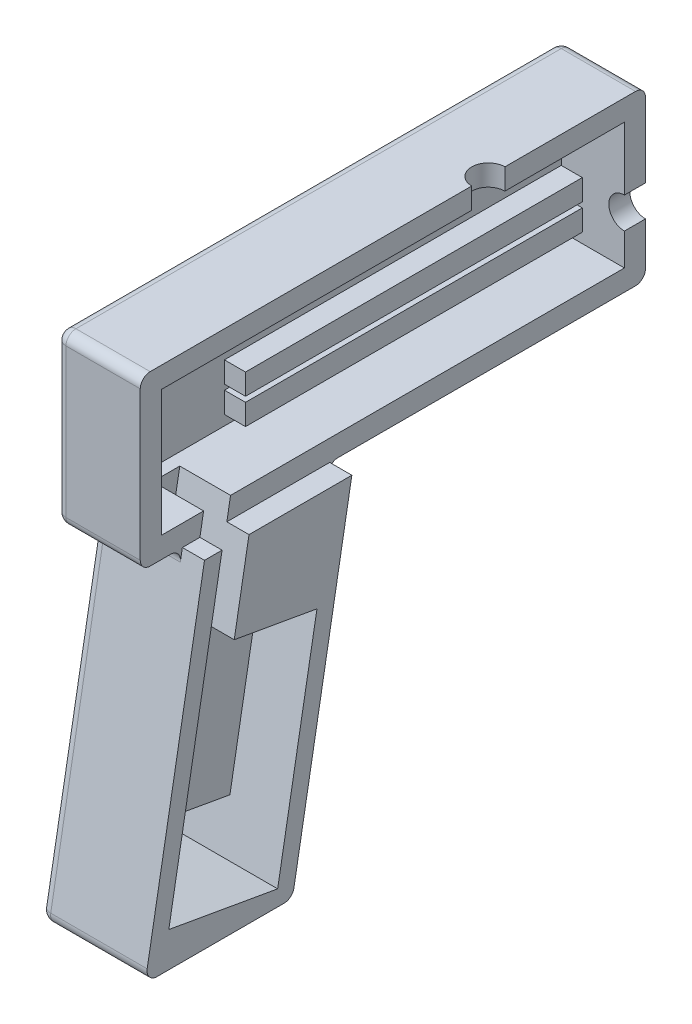
SolidWorks part; units mm, degrees
ref_plane "Front Plane" through (0, 0, 0) normal (0, 0, 1) x (1, 0, 0)
ref_plane "Top Plane" through (0, 0, 0) normal (0, 1, 0) x (1, 0, 0)
ref_plane "Right Plane" through (0, 0, 0) normal (1, 0, 0) x (0, 0, -1)
sketch "Sketch1" plane through (0, 0, 0) normal (0, 0, 1) x (1, 0, 0)
  line L1 (0, 0) -> (25.4, 0)
  line L2 (0, 0) -> (0, 50.8)
  line L3 (0, 50.8) -> (25.4, 50.8)
  line L4 (25.4, 0) -> (25.4, 50.8)
  dimension "D1" = 50.8
  dimension "D2" = 25.4
extrude "Boss-Extrude1" add sketch "Sketch1" against normal blind 152.4
sketch "Sketch2" plane through (25.4, 0, 0) normal (1, 0, 0) x (0, 0, -1)
  line L0 (0, 0) -> (0, 50.8) construction
  line L1 (6.35, 44.45) -> (146.05, 44.45)
  line L2 (6.35, 44.45) -> (6.35, 6.35)
  line L3 (6.35, 6.35) -> (146.05, 6.35)
  line L4 (146.05, 44.45) -> (146.05, 6.35)
  line L5 (152.4, 50.8) -> (0, 50.8) construction
  line L6 (152.4, 0) -> (0, 0) construction
  line L7 (152.4, 0) -> (152.4, 50.8) construction
  point P12 (6.35, 25.4)
  point P13 (0, 25.4)
  dimension "D1" = 6.35
  dimension "D2" = 6.35
  dimension "D3" = 6.35
  dimension "D4" = 6.35
extrude "Cut-Extrude1" cut sketch "Sketch2" against normal blind 19.05
sketch "Sketch4" plane through (0, 50.8, 0) normal (0, 1, 0) x (1, 0, 0)
  line L1 (25.4, 152.4) -> (25.4, 0) construction
  line L6 (0, 0) -> (25.4, 0)
  line L7 (25.4, 0) -> (25.4, 152.4)
  line L8 (25.4, 152.4) -> (0, 152.4)
  line L9 (0, 152.4) -> (0, 0)
  line L11 (25.4, 100) -> (25.4, 110)
  arc A1 (25.4, 100) -> (25.4, 110) centre (25.4, 105) cw
  dimension "D1" = 100
  dimension "D2" = 0
extrude "HitLED" cut sketch "Sketch4" against normal up to vertex (6.35 mm away) contours L11 A1 up to point (25.4, 44.45, -146.05)
sketch "Sketch5" plane through (6.35, 0, 0) normal (1, 0, 0) x (0, 0, -1)
  line L0 (44.45, 17.27) -> (146.05, 17.27)
  line L1 (44.45, 23.62) -> (146.05, 23.62)
  line L2 (44.45, 23.62) -> (44.45, 9.35)
  line L3 (44.45, 9.35) -> (146.05, 9.35)
  line L4 (146.05, 23.62) -> (146.05, 9.35)
  line L9 (44.45, 15.7) -> (146.05, 15.7)
  line L10 (6.35, 6.35) -> (146.05, 6.35) construction
  line L11 (146.05, 6.35) -> (146.05, 44.45) construction
  point P8 (0, 0)
  point P9 (0, 0)
  line M13 (146.05, 6.35) -> (146.05, 44.45)
  dimension "D1" = 1.57
  dimension "D2" = 6.35
  dimension "D3" = 6.35
  dimension "D4" = 3
  dimension "D5" = 0
  dimension "D6" = 101.6
extrude "PCB Slot" add sketch "Sketch5" along normal blind 6.35 contours L1 L2 L0 M13 | L9 L2 L3 M13 region at (6.35, 20.445, -95.25) region at (6.35, 12.525, -95.25)
sketch "Sketch7" plane through (0, 0, -146.05) normal (0, 0, 1) x (1, 0, 0)
  line L0 (25.4, 6.35) -> (25.4, 44.45) construction
  line L1 (25.4, 25.4) -> (25.4, 16)
  arc A0 (25.4, 16) -> (25.4, 25.4) centre (25.4, 20.7) cw
extrude "IRLED" cut sketch "Sketch7" against normal blind 6.35
sketch "Sketch8" plane through (0, 0, 0) normal (0, -1, 0) x (-1, 0, 0)
  line L0 (-25.4, 152.4) -> (-25.4, 0) construction
  line L1 (-25.4, 12.7) -> (-12.7, 12.7)
  line L2 (-25.4, 12.7) -> (-25.4, 57.15)
  line L3 (-25.4, 57.15) -> (-12.7, 57.15)
  line L4 (-12.7, 12.7) -> (-12.7, 57.15)
  line L5 (0, 152.4) -> (0, 0) construction
  line L6 (0, 0) -> (-25.4, 0) construction
  dimension "D1" = 12.7
  dimension "D2" = 44.45
  dimension "D3" = 12.7
extrude "HandleHole" cut sketch "Sketch8" against normal blind 6.35
sketch "Sketch10" plane through (25.4, 0, 0) normal (1, 0, 0) x (0, 0, -1)
  line L0 (12.7, 0) -> (-5.2148, -101.6)
  line L1 (-5.2148, -101.6) -> (39.2352, -101.6)
  line L2 (39.2352, -101.6) -> (57.15, 0)
  line L4 (12.7, 0) -> (57.15, 0)
  dimension "D1" = 101.6
extrude "Butt" add sketch "Sketch10" against normal up to surface (25.4 mm away) separate body up to face at (0, 25.4, -76.2)
sketch "Sketch11" plane through (25.4, 0, 0) normal (1, 0, 0) x (0, 0, -1)
  line L0 (24.1444, -25.6759) -> (23.8454, -25.6232)
  line L3 (13.7936, -23.8507) -> (1.9399, -91.0762)
  line L4 (13.7936, -23.8507) -> (46.6246, -29.6397)
  line L5 (1.9399, -91.0762) -> (34.7709, -96.8652)
  line L6 (46.6246, -29.6397) -> (34.7709, -96.8652)
  line L7 (39.2352, -101.6) -> (57.15, 0) construction
  line L8 (12.7, 0) -> (-5.2148, -101.6) construction
  dimension "D1" = 68.2625
  dimension "D2" = 33.3375
  dimension "D3" = 5.2186
extrude "BatteryPack" cut sketch "Sketch11" against normal blind 10.3187 contours L6 L4 L0 L3 L5 region at (25.4, -60.358, -24.2823)
sketch "Sketch13" plane through (15.0812, 0, 0) normal (1, 0, 0) x (0, 0, -1)
  line L0 (13.7936, -23.8507) -> (1.9399, -91.0762)
  line L1 (13.7936, -23.8507) -> (21.672, -25.2399)
  line L2 (1.9399, -91.0762) -> (9.8184, -92.4654)
  line L3 (21.672, -25.2399) -> (9.8184, -92.4654)
  line L4 (1.9399, -91.0762) -> (34.7709, -96.8652) construction
  line L5 (13.7936, -23.8507) -> (1.9399, -91.0762) construction
  line L6 (13.7936, -23.8507) -> (46.6246, -29.6397) construction
  line L7 (13.7936, -23.8507) -> (21.672, -25.2399)
  line L8 (13.7936, -23.8507) -> (21.672, -25.2399)
  line L9 (9.8184, -92.4654) -> (1.9399, -91.0762)
  line M6 (46.6246, -29.6397) -> (13.7936, -23.8507)
  line M7 (13.7936, -23.8507) -> (1.9399, -91.0762)
  line M8 (1.9399, -91.0762) -> (34.7709, -96.8652)
  dimension "D1" = 0
  dimension "D2" = 0
  dimension "D3" = 8
  dimension "D4" = 0
extrude "Wires-Battery" cut sketch "Sketch13" against normal blind 5 contours L3 M6 M7 M8 region at (15.0812, -58.1581, -11.806)
sketch "Sketch21" plane through (25.4, 0, 0) normal (1, 0, 0) x (0, 0, -1)
  line L0 (13.7936, -23.8507) -> (21.672, -25.2399)
  line L1 (13.7936, -23.8507) -> (46.6246, -29.6397) construction
  line L2 (21.672, -25.2399) -> (26.1225, 0)
  line L3 (57.15, 0) -> (12.7, 0) construction
  line L4 (26.1225, 0) -> (17.9991, 0)
  line L5 (17.9991, 0) -> (13.7936, -23.8507)
  line L6 (21.672, -25.2399) -> (9.8184, -92.4654) construction
  line L7 (13.7936, -23.8507) -> (1.9399, -91.0762) construction
  dimension "D1" = 8
extrude "Wire-Track" cut sketch "Sketch21" against normal up to surface (15.3187 mm away) contours L5 L0 L2 L4 up to face at (10.0813, -58.1581, -11.806)
sketch "Sketch23" plane through (0, 0, -12.7) normal (0, 0, -1) x (-1, 0, 0)
  line L1 (-12.7, 6.35) -> (-25.4, 6.35)
  line L2 (-12.7, 6.35) -> (-12.7, 0)
  line L3 (-12.7, 0) -> (-25.4, 0)
  line L4 (-25.4, 6.35) -> (-25.4, 0)
extrude "FixHandleHole" add sketch "Sketch23" along normal up to next
sketch "Sketch24" plane through (25.4, 0, 0) normal (1, 0, 0) x (0, 0, -1)
  line L0 (17.9991, 0) -> (19.1188, 6.35)
  line L1 (17.9991, 0) -> (26.1225, 0)
  line L2 (19.1188, 6.35) -> (27.2422, 6.35)
  line L3 (26.1225, 0) -> (27.2422, 6.35)
  line L4 (6.35, 6.35) -> (146.05, 6.35) construction
  line L5 (17.9991, 0) -> (1.9399, -91.0762) construction
  line L6 (21.672, -25.2399) -> (26.1225, 0) construction
  dimension "D1" = 8
extrude "FixHandleHole2" cut sketch "Sketch24" against normal up to surface (15.3187 mm away) up to face at (10.0813, -45.8854, -13.97)
sketch "Sketch25" plane through (15.0812, 0, 0) normal (1, 0, 0) x (0, 0, -1)
  line L0 (17.6795, -78.6201) -> (37.3757, -82.0931)
  line L1 (17.6795, -78.6201) -> (15.0748, -93.3922)
  line L2 (37.3757, -82.0931) -> (34.7709, -96.8652)
  line L3 (15.0748, -93.3922) -> (34.7709, -96.8652)
  line L4 (9.8184, -92.4654) -> (34.7709, -96.8652) construction
  line L5 (46.6246, -29.6397) -> (34.7709, -96.8652) construction
  dimension "D1" = 0
  dimension "D2" = 15
  dimension "D3" = 20
  dimension "D4" = 0
extrude "Switch Hole" cut sketch "Sketch25" against normal up to next
sketch "Sketch32" plane through (25.4, 0, 0) normal (1, 0, 0) x (0, 0, -1)
  line L0 (57.15, 0) -> (26.1225, 0)
  line L1 (21.672, -25.2399) -> (27.2422, 6.35) construction
  line L2 (26.1225, 0) -> (21.672, -25.2399)
  line L3 (21.672, -25.2399) -> (46.6246, -29.6397)
  line L4 (46.6246, -29.6397) -> (34.7709, -96.8652)
  line L5 (34.7709, -96.8652) -> (1.9399, -91.0762)
  line L6 (1.9399, -91.0762) -> (17.9991, 0)
  line L7 (19.1188, 6.35) -> (1.9399, -91.0762) construction
  line L8 (17.9991, 0) -> (12.7, 0)
  line L9 (12.7, 0) -> (-5.2148, -101.6)
  line L10 (-5.2148, -101.6) -> (39.2352, -101.6)
  line L11 (39.2352, -101.6) -> (57.15, 0)
extrude "Boss-Extrude10" add sketch "Sketch32" along normal blind 6.6813
fillet "Fillet2" radius 3 16 edges at (0, 25.4, -152.4) (0, 50.8, -76.2) (12.7, 50.8, -152.4) (12.7, 0, -152.4) (16.0406, -101.6, -39.2352) (0, -101.6, -17.0102) (12.7, 0, -12.7) (0, -50.8, -3.7426) (0, -50.8, -48.1926) (0, 0, -104.775) (12.7, 50.8, 0) (0, 25.4, 0) (12.7, 0, 0) (0, 0, -6.35) (12.7, 0, -57.15) (16.0406, -101.6, 5.2148)
